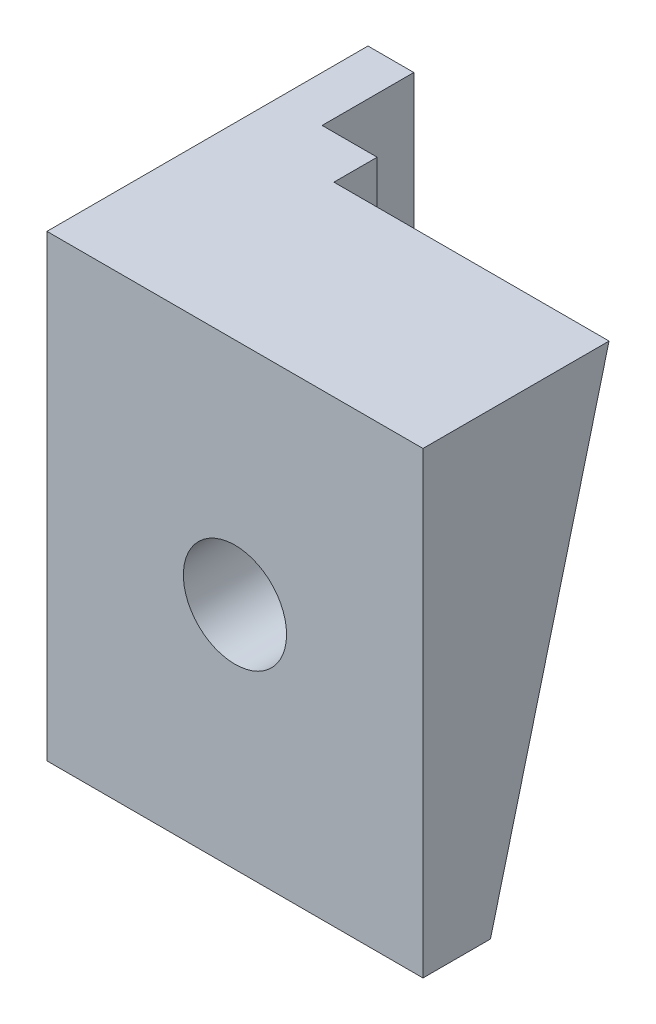
SolidWorks part; units mm, degrees
ref_plane "Front Plane" through (0, 0, 0) normal (0, 0, 1) x (1, 0, 0)
ref_plane "Top Plane" through (0, 0, 0) normal (0, 1, 0) x (1, 0, 0)
ref_plane "Right Plane" through (0, 0, 0) normal (1, 0, 0) x (0, 0, -1)
sketch "Sketch2" plane through (0, 0, 0) normal (0, 0, 1) x (1, 0, 0)
  line L1 (0, 0) -> (1, 0)
  line L2 (0, 0) -> (0, 10)
  line L3 (0, 10) -> (1, 10)
  line L4 (1, 0) -> (1, 10)
  line L5 (1, 0) -> (2.2, 0)
  line L6 (1, 0) -> (1, 10)
  line L7 (1, 10) -> (2.2, 10)
  line L8 (2.2, 0) -> (2.2, 10)
  dimension "D1" = 10
  dimension "D2" = 1
  dimension "D3" = 1.2
extrude "Boss-Extrude1" add sketch "Sketch2" along normal blind 5 contours L5 L8 L7 L4 | L1 L4 L3 L2 region at (0.5, 5, 0) region at (1.6, 5, 0)
extrude "Boss-Extrude2" add sketch "Sketch2<3>" against normal blind 2 contours L1 L4 L3 L2 region at (0.5, 5, 0)
sketch "Sketch2<3>" plane through (0, 0, 0) normal (0, 0, 1) x (1, 0, 0) same geometry as "Sketch2"
sketch "Sketch3" plane through (2.2, 0, 0) normal (1, 0, 0) x (0, 0, -1)
  line L0 (-3.529, 0) -> (-0.9429, 10)
  line L1 (-5, 0) -> (0, 0) construction
  line L2 (-5, 10) -> (0, 10) construction
  line M3 (0, 10) -> (-5, 10)
  line M4 (-5, 10) -> (-5, 0)
  line M5 (-5, 0) -> (0, 0)
  dimension "D1" = 1.471
  dimension "D2" = 75.5
extrude "Boss-Extrude3" add sketch "Sketch3" along normal blind 6 contours L0 M5 M3 M4 region at (2.2, 5.7797, 3.5171)
sketch "Sketch4" plane through (0, 0, 5) normal (0, 0, 1) x (1, 0, 0)
  line L0 (8.2, 10) -> (0, 0) construction
  line L1 (0, 10) -> (8.2, 0) construction
  circle A0 centre (4.1, 5) radius 1.125
  point P10 (4.1, 5)
  dimension "D1" = 2.25
extrude "Cut-Extrude1" cut sketch "Sketch4" against normal blind 6
